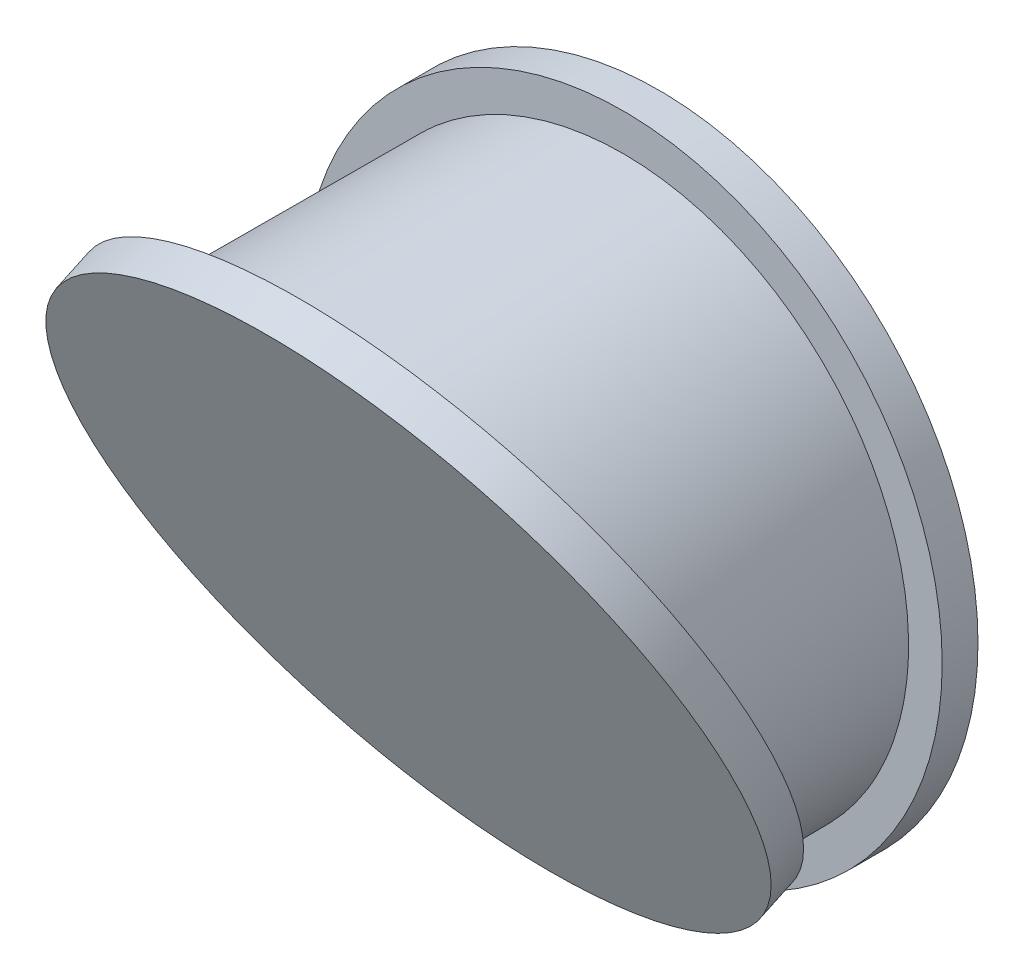
SolidWorks part; units mm, degrees
ref_plane "Front Plane" through (0, 0, 0) normal (0, 0, 1) x (1, 0, 0)
ref_plane "Top Plane" through (0, 0, 0) normal (0, 1, 0) x (1, 0, 0)
ref_plane "Right Plane" through (0, 0, 0) normal (1, 0, 0) x (0, 0, -1)
sketch "Sketch1" plane through (0, 0, 0) normal (0, 0, 1) x (1, 0, 0)
  line L0 (0, 34.9907) -> (0, -37.6588) construction
  line L1 (-13.89, -45) -> (14.3357, -45) construction
  circle A0 centre (0, 0) radius 23.75
  circle A1 centre (0, 0) radius 26.75
  point P8 (0, 23.75)
  dimension "D1" = 47.5
  dimension "D3" = 3
  dimension "D2" = 45
sketch "Sketch2" plane through (0, 0, 0) normal (1, 0, 0) x (0, 0, -1)
  line L0 (-83.7289, 0) -> (11.8569, 0) construction
  point P2 (-83.7289, 0)
ref_plane "Plane1" through (0, -8.0373, 17.236) normal (0, -0.4226, 0.9063) x (1, 0, 0)
sketch "Sketch3" plane through (0, -8.0373, 17.236) normal (0, -0.4226, 0.9063) x (1, 0, 0)
  line L0 (0, 8.8682) -> (0, 58.8682)
  line L2 (0, 19.9432) -> (0, -19.0864) construction
  circle A0 centre (0, 8.8682) radius 25
  circle A1 centre (0, 8.8682) radius 28
  point P4 (0, 33.8682)
  dimension "D1" = 50
  dimension "D2" = 3
  dimension "D3" = 50
loft "Loft1" add section "Sketch1" section "Sketch3" connector at (0.1208, 23.7497, 0) connector at (-0.0001, 22.6577, 31.5493)
extrude "Boss-Extrude1" add sketch "Sketch3<5>" against normal blind 3 contours A1
sketch "Sketch3<5>" plane through (0, -8.0373, 17.236) normal (0, -0.4226, 0.9063) x (1, 0, 0) same geometry as "Sketch3"
extrude "Boss-Extrude2" add sketch "Sketch1<4>" along normal blind 3 contours A1
sketch "Sketch1<4>" plane through (0, 0, 0) normal (0, 0, 1) x (1, 0, 0) same geometry as "Sketch1"
